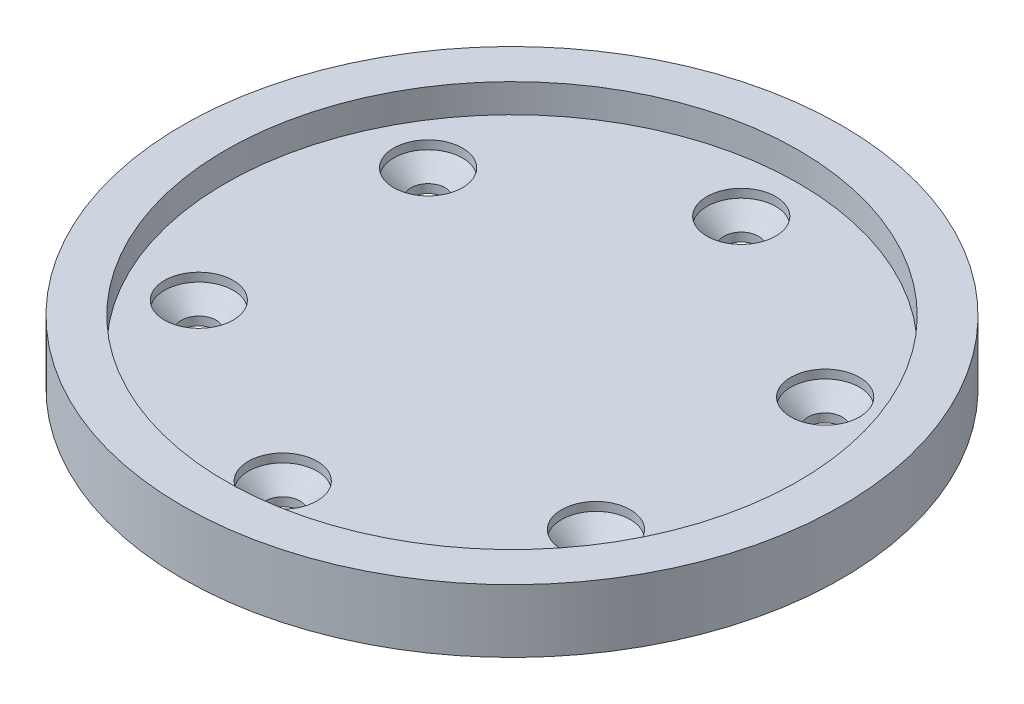
SolidWorks part; units mm, degrees
material "PBT General Purpose"
ref_plane "Front Plane" through (0, 0, 0) normal (0, 0, 1) x (1, 0, 0)
ref_plane "Top Plane" through (0, 0, 0) normal (0, 1, 0) x (1, 0, 0)
ref_plane "Right Plane" through (0, 0, 0) normal (1, 0, 0) x (0, 0, -1)
sketch "Sketch1" plane through (0, 0, 0) normal (0, 0, 1) x (1, 0, 0)
  line L0 (0, 0) -> (0, 21.4941) construction
  line L1 (50, 5.4786) -> (50, 10.4786)
  line L2 (50, 10.4786) -> (57.5, 10.4786)
  line L9 (50, 5.4786) -> (0, 5.4786)
  line L10 (0, -0.5214) -> (0, 5.4786)
  line L11 (0, -0.5214) -> (57.5, -0.5214)
  line L12 (57.5, -0.5214) -> (57.5, 10.4786)
  dimension "D1" = 0.5214
  dimension "D2" = 50
  dimension "D5" = 7.5
  dimension "D3" = 6
  dimension "D7" = 5
revolve "Revolve1" add sketch "Sketch1" angle 360 about L0
sketch "Sketch2" plane through (0, 5.4786, 0) normal (0, 1, 0) x (1, 0, 0)
  line L0 (0, 0) -> (0, 40) construction
  circle A0 centre (0, 40) radius 3
  circle A6 centre (34.641, 20) radius 3
  circle A7 centre (34.641, -20) radius 3
  circle A8 centre (0, -40) radius 3
  circle A9 centre (-34.641, -20) radius 3
  circle A10 centre (-34.641, 20) radius 3
  point P31 (0, 0)
  dimension "D1" = 6
  dimension "D2" = 40
  dimension "D3" = 6
extrude "Cut-Extrude1" cut sketch "Sketch2" against normal through all
sketch "Sketch3" plane through (0, 5.4786, 0) normal (0, 1, 0) x (1, 0, 0)
  circle A0 centre (0, 40) radius 6
  circle A1 centre (34.641, 20) radius 6
  circle A2 centre (34.641, -20) radius 6
  circle A3 centre (0, -40) radius 6
  circle A4 centre (-34.641, -20) radius 6
  circle A5 centre (-34.641, 20) radius 6
  point P3 (0, 0)
  point P18 (0, 0)
  dimension "D1" = 12
  dimension "D2" = 6
extrude "Cut-Extrude2" cut sketch "Sketch3" against normal blind 1.5
chamfer "Chamfer1" distance 3 angle 45 6 edges at (-34.641, 3.9786, -17) (-34.641, 3.9786, 23) (0, 3.9786, 43) (0, 3.9786, -37) (34.641, 3.9786, -17) (34.641, 3.9786, 23)
sketch "Avoid Area1" plane through (0, 10.4786, 0) normal (0, 1, 0) x (1, 0, 0)
  line L1 (-89.8447, 23.9111) -> (-38.4245, 23.9111)
  line L2 (-89.8447, 23.9111) -> (-89.8447, -17.7959)
  line L3 (-89.8447, -17.7959) -> (-38.4245, -17.7959)
  line L4 (-38.4245, 23.9111) -> (-38.4245, -17.7959)
  line L5 (40.0837, 23.0719) -> (89.3624, 23.0719)
  line L6 (40.0837, 23.0719) -> (40.0837, -19.2779)
  line L7 (40.0837, -19.2779) -> (89.3624, -19.2779)
  line L8 (89.3624, 23.0719) -> (89.3624, -19.2779)
  point P8 (-73.268, -26.5747)
  point P9 (-72.0465, 23.9111)
  point P10 (80.4287, 23.0968)
  point P11 (80.8358, -23.3176)
sketch "Avoid Area2" plane through (0, 10.4786, 0) normal (0, 1, 0) x (1, 0, 0)
  line L5 (-29.0326, -25.7834) -> (28.925, -25.7834)
  line L6 (-29.0326, -25.7834) -> (-29.0326, -80.3919)
  line L11 (-29.0326, -80.3919) -> (28.925, -80.3919)
  line L12 (28.925, -25.7834) -> (28.925, -80.3919)
  line L13 (-25.225, 88.174) -> (28.7215, 88.174)
  line L14 (-25.225, 88.174) -> (-25.225, 29.095)
  line L15 (-25.225, 29.095) -> (28.7215, 29.095)
  line L16 (28.7215, 88.174) -> (28.7215, 29.095)
  point P0 (0, 0)
  point P6 (0, 0)
  point P12 (28.925, -71.1569)
  point P13 (-20.7465, -70.9533)
  point P14 (28.7215, 76.0254)
  point P15 (-25.225, 74.804)
sketch3d "3DSketch3"
  point P0 (-59.5, 29.4786, 59.5)
